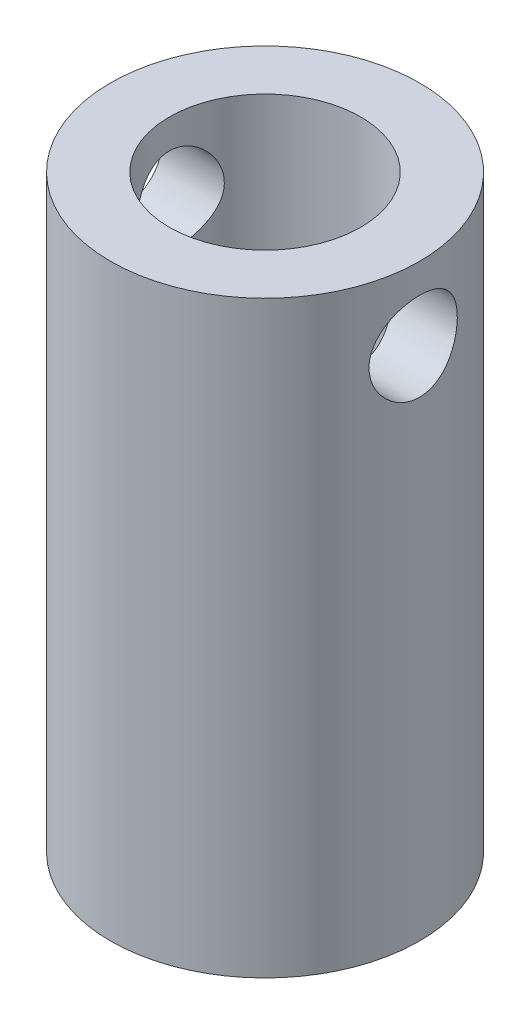
SolidWorks part; units mm, degrees
ref_plane "Front Plane" through (0, 0, 0) normal (0, 0, 1) x (1, 0, 0)
ref_plane "Top Plane" through (0, 0, 0) normal (0, 1, 0) x (1, 0, 0)
ref_plane "Right Plane" through (0, 0, 0) normal (1, 0, 0) x (0, 0, -1)
sketch "Sketch1" plane through (0, 0, 0) normal (0, 1, 0) x (1, 0, 0)
  circle A0 centre (0, 0) radius 3.25
  circle A1 centre (0, 0) radius 5.25
  dimension "D1" = 6.5
  dimension "D2" = 10.5
extrude "Boss-Extrude1" add sketch "Sketch1" along normal blind 20
sketch "Sketch2" plane through (0, 0, 0) normal (1, 0, 0) x (0, 0, -1)
  line L0 (0, 20) -> (0, 17.5) construction
  line L1 (5.25, 20) -> (-5.25, 20) construction
  circle A0 centre (0, 17.5) radius 1.5
  dimension "D2" = 3
  dimension "D1" = 2.5
extrude "Cut-Extrude1" cut sketch "Sketch2" against normal blind 20 and the other way blind 20
